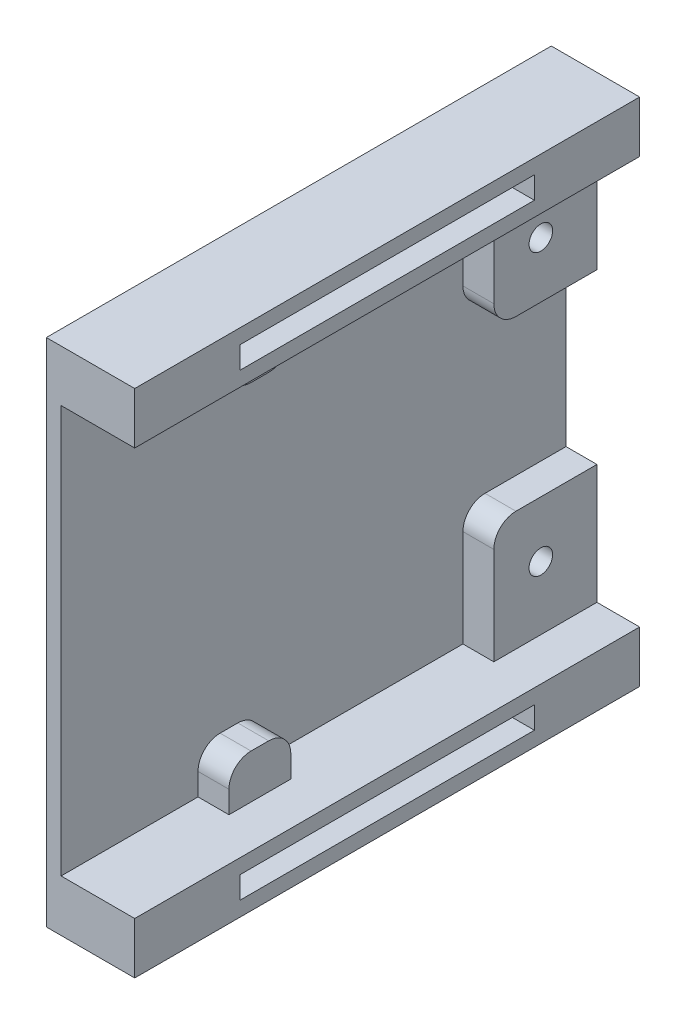
SolidWorks part; units mm, degrees
ref_plane "Front Plane" through (0, 0, 0) normal (1, 0, 0) x (0, 1, 0)
ref_plane "Top Plane" through (0, 0, 0) normal (0, 0, 1) x (0, 1, 0)
ref_plane "Right Plane" through (0, 0, 0) normal (0, 1, 0) x (-1, 0, 0)
sketch "Sketch1" plane through (0, 0, 0) normal (1, 0, 0) x (0, 1, 0)
  line L5 (-17.335, 17.145) -> (17.335, 17.145)
  line L7 (-17.335, 17.145) -> (-17.335, -17.145)
  line L8 (-17.335, -17.145) -> (17.335, -17.145)
  line L9 (17.335, 17.145) -> (17.335, -17.145)
  line L10 (-17.335, 17.145) -> (17.335, -17.145) construction
  line L11 (-17.335, -17.145) -> (17.335, 17.145) construction
  line L12 (-13.335, 17.145) -> (13.335, 17.145) construction
  line L13 (-13.335, 17.145) -> (-13.335, -17.145) construction
  line L14 (-13.335, -17.145) -> (13.335, -17.145) construction
  line L15 (13.335, 17.145) -> (13.335, -17.145) construction
  line L16 (-13.335, 17.145) -> (13.335, -17.145) construction
  line L17 (-13.335, -17.145) -> (13.335, 17.145) construction
  point P0 (0, 0)
  point P6 (0, 0)
  dimension "D1" = 34.67
  dimension "D2" = 34.29
  dimension "D3" = 34.29
  dimension "D4" = 26.67
extrude "Boss-Extrude1" add sketch "Sketch1" along normal blind 1
sketch "Sketch3" plane through (1, 0, 0) normal (1, 0, 0) x (0, 1, 0)
  line L0 (-17.335, -17.145) -> (17.335, -17.145) construction
  line L1 (-17.335, 17.145) -> (-13.835, 17.145)
  line L2 (-17.335, 17.145) -> (-17.335, -17.145)
  line L3 (-17.335, -17.145) -> (-13.835, -17.145)
  line L4 (-13.835, 17.145) -> (-13.835, -17.145)
  line L5 (17.335, 17.145) -> (-17.335, 17.145) construction
  line L6 (17.335, -17.145) -> (13.835, -17.145)
  line L7 (17.335, -17.145) -> (17.335, 17.145)
  line L8 (17.335, 17.145) -> (13.835, 17.145)
  line L9 (13.835, -17.145) -> (13.835, 17.145)
  line M3 (17.335, -17.145) -> (17.335, 17.145)
  line M4 (17.335, 17.145) -> (-17.335, 17.145)
  line M5 (-17.335, 17.145) -> (-17.335, -17.145)
  line M6 (-17.335, -17.145) -> (17.335, -17.145)
  dimension "D1" = 3.5
extrude "Boss-Extrude2" add sketch "Sketch3" along normal blind 5 contours L4 M4 M5 M6 | L9 M6 M3 M4 region at (1, -15.585, 0) region at (1, 15.585, 0)
sketch "Sketch5" plane through (6, 0, 0) normal (1, 0, 0) x (0, 1, 0)
  line L0 (0, 0) -> (0, 50000) construction
  line L1 (-16.335, -10) -> (-14.835, -10)
  line L2 (-16.335, -10) -> (-16.335, 10)
  line L3 (-16.335, 10) -> (-14.835, 10)
  line L4 (-14.835, -10) -> (-14.835, 10)
  line L5 (-16.335, -10) -> (-14.835, 10) construction
  line L6 (-16.335, 10) -> (-14.835, -10) construction
  line L7 (-17.335, 0) -> (-15.585, 0) construction
  line L8 (-17.335, 17.145) -> (-17.335, -17.145) construction
  line L9 (-15.585, 0) -> (-13.835, 0) construction
  line L10 (-13.835, 17.145) -> (-13.835, -17.145) construction
  line L11 (15.585, 0) -> (13.835, 0) construction
  line L12 (17.335, 0) -> (15.585, 0) construction
  line L13 (16.335, 10) -> (14.835, -10) construction
  line L14 (16.335, -10) -> (14.835, 10) construction
  line L15 (14.835, -10) -> (14.835, 10)
  line L16 (16.335, 10) -> (14.835, 10)
  line L17 (16.335, -10) -> (16.335, 10)
  line L18 (16.335, -10) -> (14.835, -10)
  point P0 (-15.585, 0)
  point P22 (15.585, 0)
  dimension "D1" = 1.5
  dimension "D2" = 20
extrude "Cut-Extrude1" cut sketch "Sketch5" against normal through all both and the other way through all
sketch "Sketch6" plane through (1, 0, 0) normal (1, 0, 0) x (0, 1, 0)
  line L0 (-13.835, 17.145) -> (-13.835, -17.145) construction
  line L1 (-13.835, 7.845) -> (-10.835, 7.845)
  line L2 (-13.835, 7.845) -> (-13.835, 3.645)
  line L3 (-13.835, 3.645) -> (-10.835, 3.645)
  line L4 (-10.835, 7.845) -> (-10.835, 3.645)
  line L5 (0, 0) -> (0, -49383.4727) construction
  line L6 (-13.835, -17.145) -> (-5.725, -17.145)
  line L7 (-13.835, -17.145) -> (-13.835, -10.145)
  line L8 (-13.835, -10.145) -> (-5.725, -10.145)
  line L9 (-5.725, -17.145) -> (-5.725, -10.145)
  line L10 (13.835, 17.145) -> (-13.835, 17.145) construction
  line L11 (5.725, -17.145) -> (5.725, -10.145)
  line L12 (13.835, -10.145) -> (5.725, -10.145)
  line L13 (13.835, -17.145) -> (13.835, -10.145)
  line L14 (13.835, -17.145) -> (5.725, -17.145)
  line L15 (10.835, 7.845) -> (10.835, 3.645)
  line L16 (13.835, 3.645) -> (10.835, 3.645)
  line L17 (13.835, 7.845) -> (13.835, 3.645)
  line L18 (13.835, 7.845) -> (10.835, 7.845)
  dimension "D1" = 5.725
  dimension "D2" = 7
  dimension "D3" = 9.3
  dimension "D4" = 13.5
  dimension "D5" = 3
extrude "Boss-Extrude3" add sketch "Sketch6" along normal blind 2.1
fillet "Fillet1" radius 1.5 6 edges at (2.05, 10.835, 3.645) (2.05, 10.835, 7.845) (2.05, -10.835, 3.645) (2.05, -10.835, 7.845) (2.05, 5.725, -10.145) (2.05, -5.725, -10.145)
sketch "Sketch7" plane through (3.1, 0, 0) normal (1, 0, 0) x (0, 1, 0)
  line L0 (0, 0) -> (0, -50000) construction
  line L2 (-13.835, -17.145) -> (-5.725, -17.145) construction
  circle A0 centre (-9.525, -13.335) radius 0.8
  circle A1 centre (9.525, -13.335) radius 0.8
  dimension "D3" = 1.6
  dimension "D1" = 3.81
  dimension "D2" = 9.525
extrude "Cut-Extrude2" cut sketch "Sketch7" against normal through all both and the other way through all contours A0 | A1 region at (3.1, -9.525, -13.335) region at (3.1, 9.525, -13.335)
equation "\"PCB_Width\"= 1.05in"
equation "\"PCB_Length\"= 1.35in"
equation "\"PCB_Thickness\"= 1.50404mm"
equation "\"USB_Height\"= 3.36mm"
equation "\"ZIF_Height\"= 2mm"
equation "\"Case_Thickness\"= 5mm"
